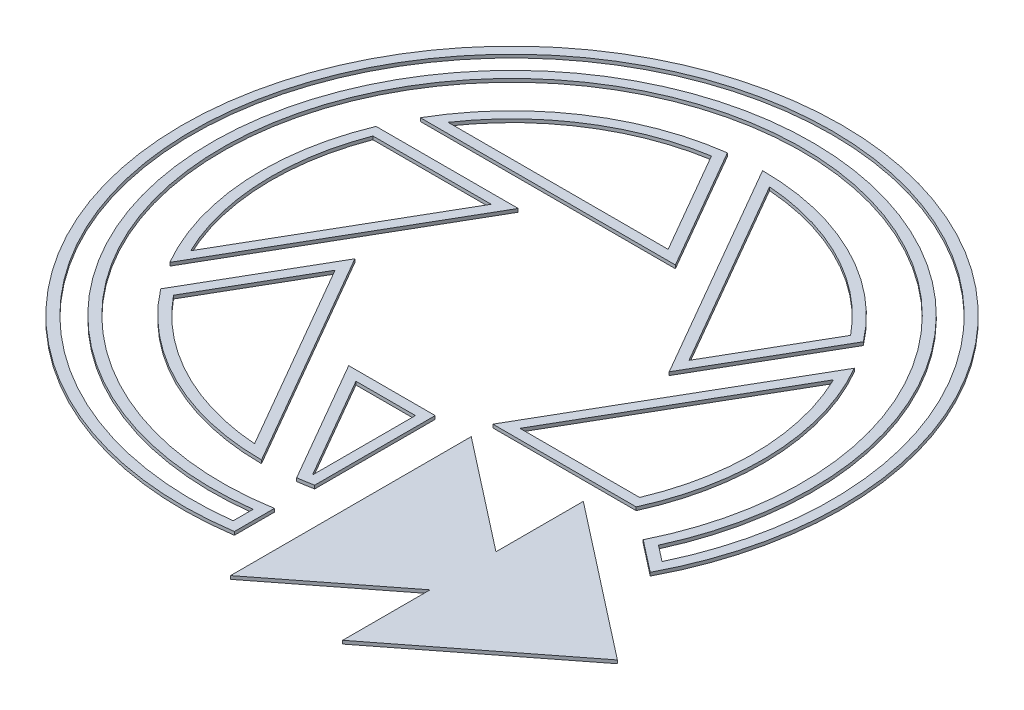
SolidWorks part; units mm, degrees
ref_plane "前视基准面" through (0, 0, 0) normal (0, 0, 1) x (1, 0, 0)
ref_plane "上视基准面" through (0, 0, 0) normal (0, 1, 0) x (1, 0, 0)
ref_plane "右视基准面" through (0, 0, 0) normal (1, 0, 0) x (0, 0, -1)
other "Configuration Table"
sketch "草图1" plane through (0, 0, 0) normal (0, 1, 0) x (1, 0, 0)
  line L0 (-2097.4547, -11.9316) -> (-770.8759, -11.9316) construction
  line L1 (-109.6966, 190) -> (-329.0897, 190)
  line L2 (128.4499, -157.5182) -> (219.3931, 0)
  line L3 (193.4123, 45) -> (109.6966, 190)
  line L4 (57.735, 190) -> (-109.6966, 190)
  line L5 (-135.6773, 145) -> (-219.3931, 0)
  line L6 (-193.4123, -45) -> (-109.6966, -190)
  line L7 (-57.735, -190) -> (73.4499, -190)
  line L8 (-135.6773, 145) -> (-351.2478, 145)
  line L9 (-219.3931, 0) -> (-329.0897, -190)
  line L10 (-193.4123, -45) -> (-301.1976, -231.6895)
  line L11 (-109.6966, -190) -> (0, -380)
  line L12 (-57.735, -190) -> (50.0502, -376.6895)
  line L13 (73.4499, -190) -> (73.4499, -372.8339)
  line L14 (-50.0502, 376.6895) -> (57.735, 190)
  line L15 (109.6966, 190) -> (0, 380)
  line L16 (219.3931, 0) -> (329.0897, 190)
  line L17 (301.1976, 231.6895) -> (193.4123, 45)
  line L18 (128.4499, -157.5182) -> (345.815, -157.5182)
  line L19 (128.4499, -190.3339) -> (128.4499, -555.3339)
  line L20 (128.4499, -555.3339) -> (298.4499, -422.8339)
  line L21 (298.4499, -422.8339) -> (298.4499, -555.3339)
  line L22 (298.4499, -555.3339) -> (532.6009, -372.8339)
  line L26 (128.4499, -372.8339) -> (532.6009, -372.8339) construction
  line L30 (298.4499, -190.3339) -> (532.6009, -372.8339)
  line L31 (298.4499, -322.8339) -> (298.4499, -190.3339)
  line L32 (128.4499, -190.3339) -> (298.4499, -322.8339)
  line L33 (73.4499, -433.8261) -> (73.4499, -494.5757)
  line L34 (394.2838, -195.2953) -> (442.4701, -232.8523)
  circle A3 centre (0, 0) radius 190 construction
  arc A4 (394.2838, -195.2953) -> (73.4499, -433.8261) centre (0, 0) ccw
  arc A5 (442.4701, -232.8523) -> (73.4499, -494.5757) centre (0, 0) ccw
  arc A6 (50.0502, -376.6895) -> (73.4499, -372.8339) centre (0, 0) ccw
  arc A7 (-301.1976, -231.6895) -> (0, -380) centre (0, 0) ccw
  arc A8 (-351.2478, 145) -> (-329.0897, -190) centre (0, 0) ccw
  arc A9 (-50.0502, 376.6895) -> (-329.0897, 190) centre (0, 0) ccw
  arc A10 (301.1976, 231.6895) -> (0, 380) centre (0, 0) ccw
  arc A11 (345.815, -157.5182) -> (329.0897, 190) centre (0, 0) ccw
  dimension "D2" = 500
  dimension "D12" = 380
  dimension "D5" = 45
  dimension "D7" = 219.3931
  dimension "D6" = 45
  dimension "D8" = 45
  dimension "D9" = 45
  dimension "D10" = 45
  dimension "D11" = 51.9615
  dimension "D14" = 55
  dimension "D13" = 365
  dimension "D15" = 170
  dimension "D16" = 100
  dimension "D17" = 55
  dimension "D3" = 60
  dimension "D4" = 60
extrude "凸台-拉伸1" add sketch "草图1" along normal blind 5
sketch "草图2" plane through (0, 5, 0) normal (0, 1, 0) x (1, 0, 0)
  line L0 (-161.6581, 130) -> (-341.0645, 130)
  line L1 (-328.5319, -159.0339) -> (-232.3835, 7.5)
  line L2 (73.4499, -494.5757) -> (73.4499, -433.8261)
  line L3 (-135.6773, 145) -> (-351.2478, 145)
  line L4 (-219.3931, 0) -> (-135.6773, 145)
  line L5 (-329.0897, -190) -> (-219.3931, 0)
  line L6 (-135.6773, 145) -> (-351.2478, 145) construction
  line L7 (-219.3931, 0) -> (-135.6773, 145) construction
  line L8 (-329.0897, -190) -> (-219.3931, 0) construction
  line L9 (73.4499, -190) -> (-57.735, -190)
  line L10 (73.4499, -372.8339) -> (73.4499, -190)
  line L11 (-57.735, -190) -> (50.0502, -376.6895)
  line L12 (73.4499, -190) -> (-57.735, -190) construction
  line L13 (73.4499, -372.8339) -> (73.4499, -190) construction
  line L14 (-57.735, -190) -> (50.0502, -376.6895) construction
  line L15 (-193.4123, -45) -> (-301.1976, -231.6895)
  line L16 (0, -380) -> (-109.6966, -190)
  line L17 (-109.6966, -190) -> (-193.4123, -45)
  line L18 (-193.4123, -45) -> (-301.1976, -231.6895) construction
  line L19 (0, -380) -> (-109.6966, -190) construction
  line L20 (-109.6966, -190) -> (-193.4123, -45) construction
  line L21 (57.735, 190) -> (-50.0502, 376.6895)
  line L22 (-329.0897, 190) -> (-109.6966, 190)
  line L23 (-109.6966, 190) -> (57.735, 190)
  line L24 (57.735, 190) -> (-50.0502, 376.6895) construction
  line L25 (-329.0897, 190) -> (-109.6966, 190) construction
  line L26 (-109.6966, 190) -> (57.735, 190) construction
  line L27 (109.6966, 190) -> (193.4123, 45)
  line L28 (0, 380) -> (109.6966, 190)
  line L29 (193.4123, 45) -> (301.1976, 231.6895)
  line L30 (109.6966, 190) -> (193.4123, 45) construction
  line L31 (0, 380) -> (109.6966, 190) construction
  line L32 (193.4123, 45) -> (301.1976, 231.6895) construction
  line L33 (329.0897, 190) -> (219.3931, 0)
  line L34 (219.3931, 0) -> (128.4499, -157.5182)
  line L35 (128.4499, -157.5182) -> (345.815, -157.5182)
  line L36 (329.0897, 190) -> (219.3931, 0) construction
  line L37 (-232.3835, 7.5) -> (-161.6581, 130)
  line L38 (58.4499, -205) -> (-31.7543, -205)
  line L39 (-31.7543, -205) -> (57.949, -360.3705)
  line L40 (58.4499, -360.2896) -> (58.4499, -205)
  line L41 (-193.4123, -75) -> (-283.1156, -230.3705)
  line L42 (-26.5385, -364.0339) -> (-122.6869, -197.5)
  line L43 (-122.6869, -197.5) -> (-193.4123, -75)
  line L51 (219.3931, 0) -> (128.4499, -157.5182) construction
  line L52 (128.4499, -157.5182) -> (345.815, -157.5182) construction
  line L53 (394.2838, -195.2953) -> (442.4701, -232.8523)
  line L54 (73.4499, -494.5757) -> (73.4499, -433.8261) construction
  line L55 (394.2838, -195.2953) -> (442.4701, -232.8523) construction
  line L56 (31.7543, 205) -> (-57.949, 360.3705)
  line L57 (-301.9934, 205) -> (-109.6966, 205)
  line L58 (-109.6966, 205) -> (31.7543, 205)
  line L59 (122.6869, 197.5) -> (193.4123, 75)
  line L60 (193.4123, 75) -> (283.1156, 230.3705)
  line L61 (26.5385, 364.0339) -> (122.6869, 197.5)
  line L62 (328.5319, 159.0339) -> (232.3835, -7.5)
  line L63 (232.3835, -7.5) -> (154.4307, -142.5182)
  line L64 (154.4307, -142.5182) -> (336.0261, -142.5182)
  line L65 (58.4499, -481.4651) -> (58.4499, -451.2301)
  line L66 (413.0236, -190.8834) -> (437.2798, -209.7889)
  arc A0 (-341.0645, 130) -> (-328.5319, -159.0339) centre (0, 0) ccw
  arc A1 (-351.2478, 145) -> (-329.0897, -190) centre (0, 0) ccw
  arc A2 (-351.2478, 145) -> (-329.0897, -190) centre (0, 0) ccw construction
  arc A3 (50.0502, -376.6895) -> (73.4499, -372.8339) centre (0, 0) ccw
  arc A4 (50.0502, -376.6895) -> (73.4499, -372.8339) centre (0, 0) ccw construction
  arc A5 (-301.1976, -231.6895) -> (0, -380) centre (0, 0) ccw
  arc A6 (-301.1976, -231.6895) -> (0, -380) centre (0, 0) ccw construction
  arc A7 (-50.0502, 376.6895) -> (-329.0897, 190) centre (0, 0) ccw
  arc A8 (-50.0502, 376.6895) -> (-329.0897, 190) centre (0, 0) ccw construction
  arc A9 (301.1976, 231.6895) -> (0, 380) centre (0, 0) ccw
  arc A10 (301.1976, 231.6895) -> (0, 380) centre (0, 0) ccw construction
  arc A11 (345.815, -157.5182) -> (329.0897, 190) centre (0, 0) ccw
  arc A12 (345.815, -157.5182) -> (329.0897, 190) centre (0, 0) ccw construction
  arc A13 (57.949, -360.3705) -> (58.4499, -360.2896) centre (0, 0) ccw
  arc A14 (394.2838, -195.2953) -> (73.4499, -433.8261) centre (0, 0) ccw
  arc A15 (442.4701, -232.8523) -> (73.4499, -494.5757) centre (0, 0) ccw
  arc A16 (394.2838, -195.2953) -> (73.4499, -433.8261) centre (0, 0) ccw construction
  arc A17 (442.4701, -232.8523) -> (73.4499, -494.5757) centre (0, 0) ccw construction
  arc A18 (-283.1156, -230.3705) -> (-26.5385, -364.0339) centre (0, 0) ccw
  arc A19 (-57.949, 360.3705) -> (-301.9934, 205) centre (0, 0) ccw
  arc A20 (283.1156, 230.3705) -> (26.5385, 364.0339) centre (0, 0) ccw
  arc A21 (336.0261, -142.5182) -> (328.5319, 159.0339) centre (0, 0) ccw
  arc A22 (413.0236, -190.8834) -> (58.4499, -451.2301) centre (0, 0) ccw
  arc A23 (437.2798, -209.7889) -> (58.4499, -481.4651) centre (0, 0) ccw
  dimension "D1" = 0
  dimension "D2" = 0
  dimension "D3" = 0
  dimension "D4" = 0
  dimension "D5" = 0
  dimension "D6" = 15
  dimension "D7" = 0
  dimension "D8" = 0
extrude "切除-拉伸1" cut sketch "草图2" against normal through all
equation "\"D6@草图1\"=\"D5@草图1\""
equation "\"D8@草图1\"=\"D5@草图1\""
equation "\"D10@草图1\"=\"D5@草图1\""
equation "\"D14@草图1\"=\"D17@草图1\""
equation "\"D4@草图1\"=\"D3@草图1\""
